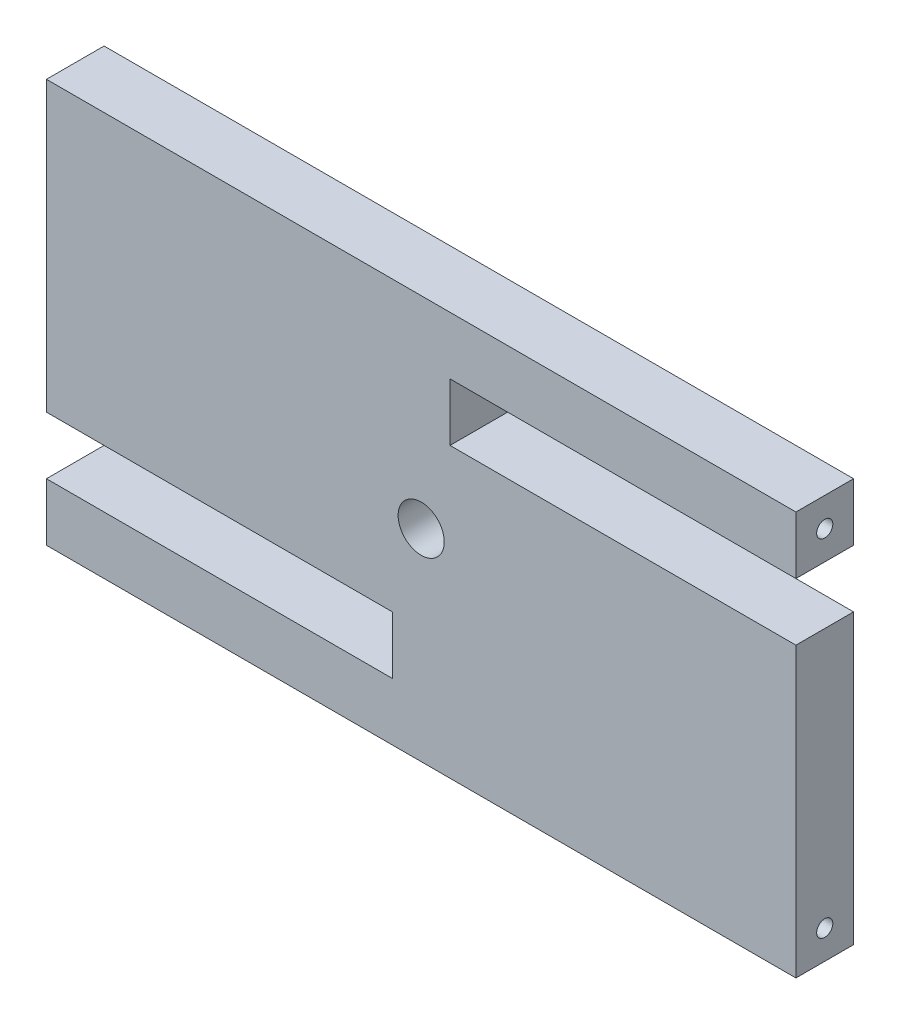
SolidWorks part; units mm, degrees
ref_plane "Front Plane" through (0, 0, 0) normal (0, 0, 1) x (1, 0, 0)
ref_plane "Top Plane" through (0, 0, 0) normal (0, 1, 0) x (1, 0, 0)
ref_plane "Right Plane" through (0, 0, 0) normal (1, 0, 0) x (0, 0, -1)
sketch "Sketch1" plane through (0, 0, 0) normal (0, 0, 1) x (1, 0, 0)
  line L0 (-115, 35) -> (15, 35)
  line L1 (15, 35) -> (15, 25)
  line L2 (15, -35) -> (-115, -35)
  line L3 (-115, -35) -> (-115, -25)
  line L4 (-115, 0) -> (115, 0) construction
  line L5 (-50, 35) -> (-50, -35) construction
  line L6 (-115, -25) -> (-55, -25)
  line L7 (-55, -25) -> (-55, -15)
  line L8 (-55, -15) -> (-115, -15)
  line L9 (15, 25) -> (-45, 25)
  line L10 (-45, 25) -> (-45, 15)
  line L11 (-45, 15) -> (15, 15)
  line L12 (-115, -15) -> (-115, 35)
  line L13 (15, 15) -> (15, -35)
  circle A1 centre (-50, 0) radius 4
  point P8 (0, 0)
  dimension "D3" = 8
  dimension "D1" = 70
  dimension "D2" = 130
  dimension "D4" = 10
  dimension "D5" = 10
  dimension "D6" = 10
  dimension "D7" = 10
  dimension "D8" = 60
  dimension "D9" = 60
  dimension "D10" = 35
extrude "Boss-Extrude2" add sketch "Sketch1" along normal blind 10
sketch "Sketch2" plane through (-115, 0, 0) normal (-1, 0, 0) x (0, 0, 1)
  line L0 (0, -25) -> (0, -35) construction
  line L1 (0, -35) -> (10, -35) construction
  line L2 (10, -35) -> (10, -25) construction
  line L3 (10, -25) -> (0, -25) construction
  line L6 (10, -15) -> (10, 35) construction
  line L7 (10, 35) -> (0, 35) construction
  line L8 (10, -35) -> (0, -35) construction
  line L9 (10, -25) -> (10, -35) construction
  line L11 (0, -25) -> (0, -35) construction
  line L12 (0, -35) -> (10, -35) construction
  line L13 (10, -35) -> (10, -25) construction
  line L14 (10, -25) -> (0, -25) construction
  line L17 (10, -15) -> (10, 35) construction
  line L18 (10, 35) -> (0, 35) construction
  line L19 (10, -35) -> (0, -35)
  line L20 (10, -25) -> (10, -35)
  line L21 (0, 35) -> (0, 25) construction
  line L22 (0, -25) -> (10, -35) construction
  line L23 (0, -35) -> (10, -25) construction
  line L24 (0, 35) -> (0, -15) construction
  line L25 (0, 25) -> (10, 25) construction
  line L26 (10, 25) -> (10, 35) construction
  line L27 (0, 35) -> (10, 25) construction
  circle A0 centre (5, 30) radius 1.4
  circle A1 centre (5, -30) radius 1.4
  dimension "D2" = 2.8
  dimension "D1" = 10
extrude "Cut-Extrude1" cut sketch "Sketch2" against normal blind 10 contours A1 | A0 | A0 region at (-115, 30, 5) region at (-115, -30, 5)
ref_plane "Plane1" through (-25, 0, 0) normal (1, 0, 0) x (0, 0, -1)
sketch "Sketch3" plane through (15, 0, 0) normal (1, 0, 0) x (0, 0, -1)
  line L0 (-5, 30) -> (0, 30) construction
  line L1 (0, 25) -> (0, 35) construction
  line L2 (-5, 30) -> (-5, 35) construction
  line L3 (-10, 35) -> (0, 35) construction
  line L4 (-5, -30) -> (-5, -35) construction
  line L5 (-10, -35) -> (0, -35) construction
  circle A0 centre (-5, -30) radius 1.4
  circle A1 centre (-5, 30) radius 1.4
  dimension "D1" = 2.8
  dimension "D2" = 2.8
  dimension "D3" = 5
extrude "Cut-Extrude2" cut sketch "Sketch3" against normal blind 10
ref_plane "Plane2" through (-50, 0, 0) normal (1, 0, 0) x (0, 0, -1)
